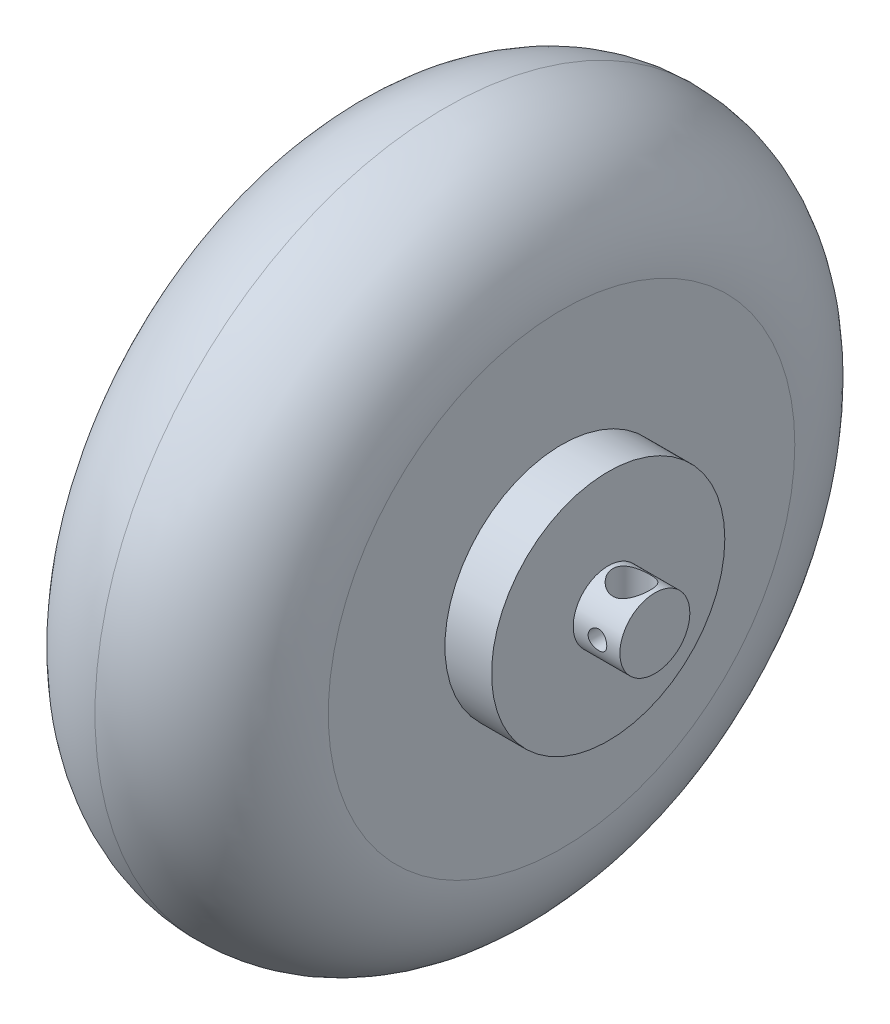
SolidWorks part; units mm, degrees
ref_plane "Ön Düzlem" through (0, 0, 0) normal (0, 0, 1) x (1, 0, 0)
ref_plane "Üst Düzlem" through (0, 0, 0) normal (0, 1, 0) x (1, 0, 0)
ref_plane "Sağ Düzlem" through (0, 0, 0) normal (1, 0, 0) x (0, 0, -1)
sketch "Çizim1" plane through (0, 0, 0) normal (1, 0, 0) x (0, 0, -1)
  line L0 (0, 25) -> (0, -25) construction
  circle A0 centre (0, 0) radius 25
  circle A1 centre (0, 0) radius 75
  dimension "D1" = 50
  dimension "D2" = 150
extrude "Yükseklik-Ekstrüzyon2" add sketch "Çizim1" along normal blind 50 contours A0 | A1
fillet "Radyus2" radius 25 2 edges at (50, 0, -75) (0, 0, -75)
sketch "Çizim2" plane through (0, 0, 0) normal (1, 0, 0) x (0, 0, -1)
  circle A0 centre (0, 0) radius 25
extrude "Yükseklik-Ekstrüzyon3" add sketch "Çizim2" along normal blind 60 and the other way blind 10
sketch "Çizim3" plane through (60, 0, 0) normal (1, 0, 0) x (0, 0, -1)
  circle A0 centre (0, 0) radius 7.5
  dimension "D1" = 15
extrude "Yükseklik-Ekstrüzyon5" add sketch "Çizim3" along normal blind 10
sketch "Çizim4" plane through (0, 0, 0) normal (0, 1, 0) x (1, 0, 0)
  circle A0 centre (65, 0) radius 4
  dimension "D1" = 8
extrude "Kes-Ekstrüzyon1" cut sketch "Çizim4" against normal blind 10 and the other way blind 10
sketch "Çizim5" plane through (-10, 0, 0) normal (-1, 0, 0) x (0, 0, 1)
  circle A0 centre (0, 0) radius 7.5
  dimension "D1" = 15
extrude "Yükseklik-Ekstrüzyon6" add sketch "Çizim5" along normal blind 10
sketch "Çizim6" plane through (0, 0, 0) normal (0, 1, 0) x (1, 0, 0)
  circle A0 centre (-15, 0) radius 4
  dimension "D1" = 8
extrude "Kes-Ekstrüzyon2" cut sketch "Çizim6" against normal blind 10 and the other way blind 10
sketch "Çizim7" plane through (0, 0, 0) normal (0, 0, 1) x (1, 0, 0)
  circle A0 centre (65.1947, 0) radius 2
  dimension "D1" = 4
extrude "Kes-Ekstrüzyon3" cut sketch "Çizim7" against normal blind 10 and the other way blind 10
sketch "Çizim8" plane through (0, 0, 0) normal (0, 0, 1) x (1, 0, 0)
  circle A0 centre (-15.1643, 0) radius 2
  dimension "D1" = 4
extrude "Kes-Ekstrüzyon4" cut sketch "Çizim8" against normal blind 10 and the other way blind 10
scale "Ölçek2" scale about centroid uniform scaling yes scale factor 0.5
